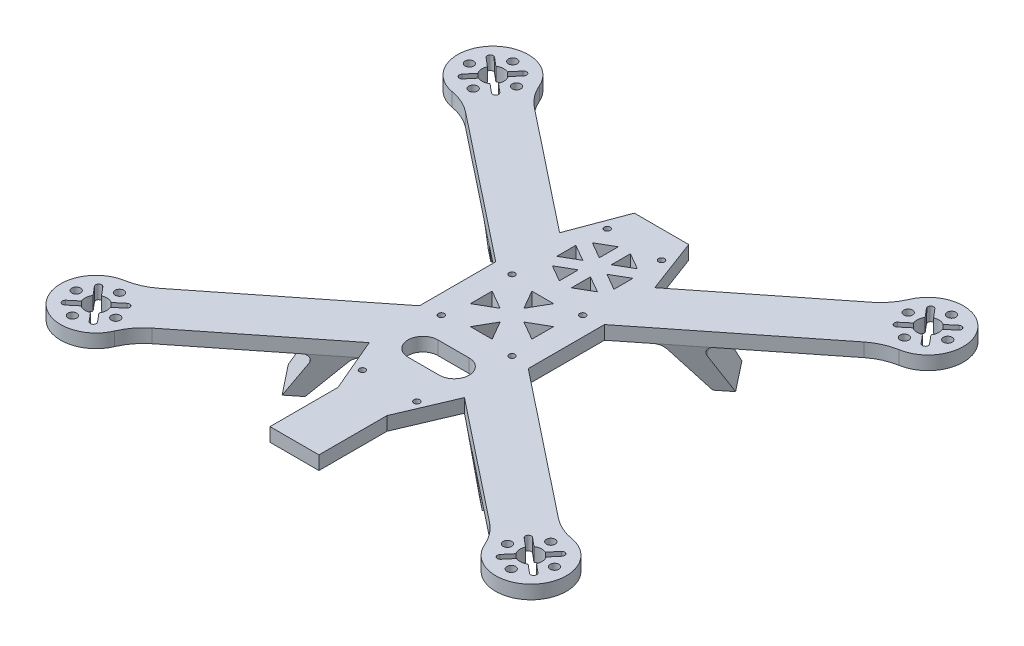
SolidWorks part; units mm, degrees
ref_plane "Front Plane" through (0, 0, 0) normal (0, 0, 1) x (1, 0, 0)
ref_plane "Top Plane" through (0, 0, 0) normal (0, 1, 0) x (1, 0, 0)
ref_plane "Right Plane" through (0, 0, 0) normal (1, 0, 0) x (0, 0, -1)
ref_axis "X Axis" through (-102.512, 0, 0) along (1, 0, 0)
ref_axis "Y Axis" through (0, 0, -107.1526) along (0, 0, 1)
ref_axis "Z Axis" through (0, 27.7441, 0) along (0, -1, 0)
ref_plane "Prop Guards Plane" through (0, 15, 0) normal (0, 1, 0) x (1, 0, 0)
ref_plane "Motor mount plane" through (0, 0, 0) normal (0, 1, 0) x (1, 0, 0)
sketch "Sketch1" plane through (0, 0, 0) normal (0, 1, 0) x (1, 0, 0)
  line L2 (-80, 73) -> (-80, 0) construction
  line L21 (-64.77, 0) -> (64.77, 0) construction
  line L22 (0, 59.69) -> (0, 20.32) construction
  line L25 (-93, 73) -> (-67, 73) construction
  line L27 (-80, 86) -> (-80, 60) construction
  line L36 (-88.3562, 63.0414) -> (-71.6438, 82.9586) construction
  line L38 (-89.9586, 81.3562) -> (-70.0414, 64.6438) construction
  line L40 (-85.1423, 66.8716) -> (-74.8577, 79.1284) construction
  line L41 (-85.9849, 67.5787) -> (-83.3147, 70.761)
  line L42 (-84.2997, 66.1646) -> (-81.6294, 69.3469)
  line L43 (-86.1284, 78.1423) -> (-73.8716, 67.8577) construction
  line L44 (-85.4213, 78.9849) -> (-82.239, 76.3147)
  line L45 (-86.8354, 77.2997) -> (-83.6531, 74.6294)
  line L49 (-78.3706, 76.6531) -> (-75.7003, 79.8354)
  line L50 (-77.761, 69.6853) -> (-74.5787, 67.0151)
  line L51 (-76.3469, 71.3706) -> (-73.1646, 68.7003)
  line L52 (-76.6853, 75.239) -> (-74.0151, 78.4213)
  line L53 (-80, 73) -> (0, 73) construction
  line L54 (-83.3147, 70.761) -> (-81.6294, 69.3469) construction
  line L56 (-77.761, 69.6853) -> (-76.3469, 71.3706) construction
  line L59 (-78.3706, 76.6531) -> (-76.6853, 75.239) construction
  line L61 (-82.239, 76.3147) -> (-83.6531, 74.6294) construction
  line L62 (0, -49.9102) -> (0, 49.9102) construction
  line L63 (78.3706, 76.6531) -> (75.7003, 79.8354)
  line L64 (76.6853, 75.239) -> (74.0151, 78.4213)
  line L65 (76.3469, 71.3706) -> (73.1646, 68.7003)
  line L66 (77.761, 69.6853) -> (74.5787, 67.0151)
  line L67 (84.2997, 66.1646) -> (81.6294, 69.3469)
  line L68 (85.9849, 67.5787) -> (83.3147, 70.761)
  line L69 (86.8354, 77.2997) -> (83.6531, 74.6294)
  line L70 (85.4213, 78.9849) -> (82.239, 76.3147)
  line L73 (-47.4403, 0) -> (47.4403, 0) construction
  line L85 (85.4213, -78.9849) -> (82.239, -76.3147)
  line L86 (86.8354, -77.2997) -> (83.6531, -74.6294)
  line L87 (85.9849, -67.5787) -> (83.3147, -70.761)
  line L88 (84.2997, -66.1646) -> (81.6294, -69.3469)
  line L89 (77.761, -69.6853) -> (74.5787, -67.0151)
  line L90 (76.3469, -71.3706) -> (73.1646, -68.7003)
  line L91 (76.6853, -75.239) -> (74.0151, -78.4213)
  line L92 (78.3706, -76.6531) -> (75.7003, -79.8354)
  line L93 (-76.6853, -75.239) -> (-74.0151, -78.4213)
  line L94 (-76.3469, -71.3706) -> (-73.1646, -68.7003)
  line L95 (-77.761, -69.6853) -> (-74.5787, -67.0151)
  line L96 (-78.3706, -76.6531) -> (-75.7003, -79.8354)
  line L97 (-86.8354, -77.2997) -> (-83.6531, -74.6294)
  line L98 (-85.4213, -78.9849) -> (-82.239, -76.3147)
  line L99 (-84.2997, -66.1646) -> (-81.6294, -69.3469)
  line L100 (-85.9849, -67.5787) -> (-83.3147, -70.761)
  line L101 (-87.9696, 72.3028) -> (-79.3028, 65.0304) construction
  line L102 (-79.3028, 65.0304) -> (-72.0304, 73.6972) construction
  line L103 (-72.0304, 73.6972) -> (-80.6972, 80.9696) construction
  line L104 (-80.6972, 80.9696) -> (-87.9696, 72.3028) construction
  circle A0 centre (-80, 73) radius 13
  circle A7 centre (-80, 73) radius 8 construction
  circle A9 centre (-87.9696, 72.3028) radius 1.6
  circle A10 centre (-79.3028, 65.0304) radius 1.6
  circle A11 centre (-80.6972, 80.9696) radius 1.6
  circle A12 centre (-72.0304, 73.6972) radius 1.6
  arc A13 (-83.6531, 74.6294) -> (-83.3147, 70.761) centre (-80, 73) ccw
  arc A14 (-85.9849, 67.5787) -> (-84.2997, 66.1646) centre (-85.1423, 66.8716) ccw
  arc A15 (-74.0151, 78.4213) -> (-75.7003, 79.8354) centre (-74.8577, 79.1284) ccw
  arc A16 (-85.4213, 78.9849) -> (-86.8354, 77.2997) centre (-86.1284, 78.1423) ccw
  arc A17 (-74.5787, 67.0151) -> (-73.1646, 68.7003) centre (-73.8716, 67.8577) ccw
  arc A18 (-81.6294, 69.3469) -> (-77.761, 69.6853) centre (-80, 73) ccw
  arc A19 (-76.3469, 71.3706) -> (-76.6853, 75.239) centre (-80, 73) ccw
  arc A20 (-78.3706, 76.6531) -> (-82.239, 76.3147) centre (-80, 73) ccw
  circle A21 centre (72.0304, 73.6972) radius 1.6
  circle A22 centre (79.3028, 65.0304) radius 1.6
  circle A23 centre (87.9696, 72.3028) radius 1.6
  circle A24 centre (80.6972, 80.9696) radius 1.6
  arc A25 (74.0151, 78.4213) -> (75.7003, 79.8354) centre (74.8577, 79.1284) cw
  arc A26 (76.3469, 71.3706) -> (76.6853, 75.239) centre (80, 73) cw
  arc A27 (74.5787, 67.0151) -> (73.1646, 68.7003) centre (73.8716, 67.8577) cw
  arc A28 (81.6294, 69.3469) -> (77.761, 69.6853) centre (80, 73) cw
  arc A29 (85.9849, 67.5787) -> (84.2997, 66.1646) centre (85.1423, 66.8716) cw
  arc A30 (83.6531, 74.6294) -> (83.3147, 70.761) centre (80, 73) cw
  arc A31 (85.4213, 78.9849) -> (86.8354, 77.2997) centre (86.1284, 78.1423) cw
  arc A32 (78.3706, 76.6531) -> (82.239, 76.3147) centre (80, 73) cw
  circle A33 centre (80, 73) radius 13
  circle A35 centre (80, -73) radius 13
  arc A36 (78.3706, -76.6531) -> (82.239, -76.3147) centre (80, -73) ccw
  arc A37 (85.4213, -78.9849) -> (86.8354, -77.2997) centre (86.1284, -78.1423) ccw
  arc A38 (83.6531, -74.6294) -> (83.3147, -70.761) centre (80, -73) ccw
  arc A39 (85.9849, -67.5787) -> (84.2997, -66.1646) centre (85.1423, -66.8716) ccw
  arc A40 (81.6294, -69.3469) -> (77.761, -69.6853) centre (80, -73) ccw
  arc A41 (74.5787, -67.0151) -> (73.1646, -68.7003) centre (73.8716, -67.8577) ccw
  arc A42 (76.3469, -71.3706) -> (76.6853, -75.239) centre (80, -73) ccw
  arc A43 (74.0151, -78.4213) -> (75.7003, -79.8354) centre (74.8577, -79.1284) ccw
  circle A44 centre (80.6972, -80.9696) radius 1.6
  circle A45 centre (87.9696, -72.3028) radius 1.6
  circle A46 centre (79.3028, -65.0304) radius 1.6
  circle A47 centre (72.0304, -73.6972) radius 1.6
  arc A48 (-78.3706, -76.6531) -> (-82.239, -76.3147) centre (-80, -73) cw
  arc A49 (-76.3469, -71.3706) -> (-76.6853, -75.239) centre (-80, -73) cw
  arc A50 (-81.6294, -69.3469) -> (-77.761, -69.6853) centre (-80, -73) cw
  arc A51 (-74.5787, -67.0151) -> (-73.1646, -68.7003) centre (-73.8716, -67.8577) cw
  arc A52 (-85.4213, -78.9849) -> (-86.8354, -77.2997) centre (-86.1284, -78.1423) cw
  arc A53 (-74.0151, -78.4213) -> (-75.7003, -79.8354) centre (-74.8577, -79.1284) cw
  arc A54 (-85.9849, -67.5787) -> (-84.2997, -66.1646) centre (-85.1423, -66.8716) cw
  arc A55 (-83.6531, -74.6294) -> (-83.3147, -70.761) centre (-80, -73) cw
  circle A56 centre (-72.0304, -73.6972) radius 1.6
  circle A57 centre (-80.6972, -80.9696) radius 1.6
  circle A58 centre (-79.3028, -65.0304) radius 1.6
  circle A59 centre (-87.9696, -72.3028) radius 1.6
  circle A60 centre (-80, -73) radius 13
  point P0 (0, 0)
  point P6 (0, 0)
  point P36 (-80, 73)
  point P53 (-80, 73)
  point P155 (-80, -73)
  point P156 (-80, -73)
  point P179 (0, 0)
  dimension "D3" = 26
  dimension "D4" = 16
  dimension "D7" = 1.1
  dimension "D5" = 3.2
  dimension "D6" = 40
  dimension "D9" = 16
  dimension "D8" = 8
  dimension "D10" = 2.2
  dimension "D2" = 80
  dimension "D11" = 73
extrude "Boss-Extrude3" add sketch "Sketch1" along normal blind 5
sketch "Sketch29" plane through (0, 0, 0) normal (0, 1, 0) x (1, 0, 0)
  line L5 (-67.0587, 74.2337) -> (-17.5, 35)
  line L6 (-17.5, -35) -> (17.5, -35)
  line L9 (-42.2793, 54.6169) -> (-53.452, 40.504) construction
  line L10 (-79.8381, 72.8718) -> (-47.8656, 47.5604) construction
  line L11 (-20, -14.0214) -> (-20, 14.0214)
  line L15 (-17.5, 35) -> (17.5, 35)
  line L22 (20, -14.0214) -> (20, 14.0214)
  line L23 (-17.5, -35) -> (17.5, 35) construction
  line L24 (-13, -13) -> (13, -13) construction
  line L25 (-13, -13) -> (-13, 13) construction
  line L26 (-13, 13) -> (13, 13) construction
  line L27 (13, -13) -> (13, 13) construction
  line L28 (-13, -13) -> (13, 13) construction
  line L29 (-13, 13) -> (13, -13) construction
  line L30 (-17.5, 35) -> (17.5, -35) construction
  line L31 (-78.2313, 60.1209) -> (-20, 14.0214)
  line L32 (42.2793, 54.6169) -> (53.452, 40.504) construction
  line L33 (49.1156, -37.0711) -> (37.943, -51.184) construction
  line L35 (-47.4403, 0) -> (47.4403, 0) construction
  line L36 (-67.0587, -74.2337) -> (-17.5, -35)
  line L37 (-78.2313, -60.1209) -> (-20, -14.0214)
  line L38 (0, -49.9102) -> (0, 49.9102) construction
  line L39 (67.0587, 74.2337) -> (17.5, 35)
  line L40 (78.2313, 60.1209) -> (20, 14.0214)
  line L41 (67.0587, -74.2337) -> (17.5, -35)
  line L42 (78.2313, -60.1209) -> (20, -14.0214)
  line L46 (0, -27) -> (0, 0) construction
  line L47 (-49.1156, -37.0711) -> (-37.943, -51.184) construction
  circle A1 centre (-13, 13) radius 1.1
  circle A2 centre (13, 13) radius 1.1
  circle A3 centre (13, -13) radius 1.1
  circle A4 centre (-13, -13) radius 1.1
  circle A11 centre (-80, 73) radius 13 construction
  circle A13 centre (-80, -73) radius 13 construction
  arc A14 (78.2313, -60.1209) -> (67.0587, -74.2337) centre (80, -73) ccw
  arc A15 (-78.2313, -60.1209) -> (-67.0587, -74.2337) centre (-80, -73) cw
  circle A16 centre (80, -73) radius 13 construction
  circle A17 centre (80, 73) radius 13 construction
  arc A18 (67.0587, 74.2337) -> (78.2313, 60.1209) centre (80, 73) ccw
  arc A20 (-67.0587, 74.2337) -> (-78.2313, 60.1209) centre (-80, 73) cw
  point P0 (0, 0)
  point P1 (0, 0)
  point P5 (0, 0)
  point P21 (0, 0)
  point P62 (-47.8656, 47.5604)
  dimension "D5" = 2.2
  dimension "D6" = 27
  dimension "D3" = 18
  dimension "D9" = 40
  dimension "D1" = 35
  dimension "D2" = 70
  dimension "D4" = 26
extrude "Boss-Extrude19" add sketch "Sketch29" along normal up to surface (5 mm away) up to face at (-80.6972, 5, -79.3696)
sketch "Sketch32" plane through (0, 0, 0) normal (0, 1, 0) x (1, 0, 0)
  line L0 (0, 0) -> (0, 55) construction
  line L1 (0, 0) -> (0, -80) construction
  line L4 (-10, 55) -> (-17.5, 35)
  line L6 (10, 55) -> (17.5, 35)
  line L7 (-10, 55) -> (10, 55)
  line L8 (-17.5, 35) -> (17.5, 35)
  line L9 (-9, -80) -> (9, -80)
  line L10 (-9, -80) -> (-9, -55)
  line L11 (-9, -55) -> (-17.5, -35)
  line L12 (-17.5, -35) -> (17.5, -35)
  line L13 (17.5, -35) -> (9, -55)
  line L14 (9, -55) -> (9, -80)
  line L15 (-9, -55) -> (9, -55) construction
  point P15 (0, -80)
  dimension "D1" = 55
  dimension "D2" = 20
  dimension "D3" = 80
  dimension "D5" = 18
extrude "Boss-Extrude20" add sketch "Sketch32" along normal up to surface (5 mm away) up to face at (-80.6972, 5, -79.3696)
sketch "Sketch33" plane through (0, 5, 0) normal (0, 1, 0) x (1, 0, 0)
  line L0 (0, 0) -> (0, -27) construction
  line L1 (-5.75, -27) -> (5.75, -27) construction
  line L2 (-5.75, -21.5) -> (5.75, -21.5)
  line L3 (-5.75, -32.5) -> (5.75, -32.5)
  line L4 (0, 19.5324) -> (0, -19.5324) construction
  line L5 (-9, 0) -> (0, 0) construction
  line L6 (-4.3812, 0) -> (-11.3094, 4)
  line L7 (-11.3094, 4) -> (-11.3094, -4)
  line L8 (-11.3094, -4) -> (-4.3812, 0)
  line L9 (0, 4.3812) -> (4, 11.3094)
  line L13 (4, 11.3094) -> (-4, 11.3094)
  line L14 (-4, 11.3094) -> (0, 4.3812)
  line L15 (4.3812, 0) -> (11.3094, -4)
  line L16 (11.3094, -4) -> (11.3094, 4)
  line L17 (11.3094, 4) -> (4.3812, 0)
  line L18 (0, -4.3812) -> (-4, -11.3094)
  line L19 (-4, -11.3094) -> (4, -11.3094)
  line L20 (4, -11.3094) -> (0, -4.3812)
  line L21 (-10, -45) -> (10, -45) construction
  line L22 (-10, 45) -> (10, 45) construction
  line L23 (-4.445, 30.48) -> (4.445, 30.48) construction
  line L24 (-4.445, 30.48) -> (-10.5072, 33.98)
  line L25 (-10.5072, 33.98) -> (-10.5072, 26.98)
  line L26 (-10.5072, 26.98) -> (-4.445, 30.48)
  line L27 (-2.2225, 34.3295) -> (-2.2225, 41.3295)
  line L28 (-2.2225, 41.3295) -> (-8.2847, 37.8295)
  line L29 (-8.2847, 37.8295) -> (-2.2225, 34.3295)
  line L30 (2.2225, 34.3295) -> (8.2847, 37.8295)
  line L31 (8.2847, 37.8295) -> (2.2225, 41.3295)
  line L32 (2.2225, 41.3295) -> (2.2225, 34.3295)
  line L33 (4.445, 30.48) -> (10.5072, 26.98)
  line L34 (10.5072, 26.98) -> (10.5072, 33.98)
  line L35 (10.5072, 33.98) -> (4.445, 30.48)
  line L36 (2.2225, 26.6305) -> (2.2225, 19.6305)
  line L37 (2.2225, 19.6305) -> (8.2847, 23.1305)
  line L38 (8.2847, 23.1305) -> (2.2225, 26.6305)
  line L39 (-2.2225, 26.6305) -> (-8.2847, 23.1305)
  line L40 (-8.2847, 23.1305) -> (-2.2225, 19.6305)
  line L41 (-2.2225, 19.6305) -> (-2.2225, 26.6305)
  arc A0 (-5.75, -21.5) -> (-5.75, -32.5) centre (-5.75, -27) ccw
  arc A1 (5.75, -32.5) -> (5.75, -21.5) centre (5.75, -27) ccw
  circle A2 centre (-9, 0) radius 2.3094 construction
  circle A3 centre (-10, -45) radius 1.1
  circle A4 centre (10, -45) radius 1.1
  circle A5 centre (-10, 45) radius 1.1
  circle A6 centre (10, 45) radius 1.1
  point P5 (0, -27)
  point P19 (0, -45)
  point P29 (0, 0)
  point P34 (0, 45)
  point P39 (-5.715, 30.48)
  point P40 (-4.445, 30.48)
  point P45 (0, 30.48)
  point P54 (0, 30.48)
  dimension "D3" = 11.5
  dimension "D8" = 2.2
  dimension "D11" = 7
  dimension "D1" = 27
  dimension "D2" = 11
  dimension "D4" = 8
  dimension "D5" = 9
  dimension "D7" = 45
  dimension "D9" = 20
  dimension "D10" = 45
  dimension "D6" = 4
  dimension "D12" = 6
extrude "Cut-Extrude1" cut sketch "Sketch33" against normal up to surface (5 mm away) contours L3 A1 L2 A0 | L6 L7 L8 | L15 L16 L17 | L9 L13 L14 | L18 L19 L20 | A5 | A6 | A3 | A4 | L27 L28 L29 | L24 L25 L26 | L33 L34 L35 | L30 L31 L32 | L39 L40 L41 | L36 L37 L38 up to face at (-72.0304, 0, -72.0972)
ref_plane "Stands Plane" through (0, -15, 0) normal (0, 1, 0) x (1, 0, 0)
sketch "Sketch30" plane through (0, -15, 0) normal (0, 1, 0) x (1, 0, 0)
  line L4 (-38.7981, -40.382) -> (0, 0) construction
  line L5 (-44.3728, -33.3164) -> (-33.2234, -47.4476) construction
  line L7 (-45.4952, -36.7558) -> (-36.8053, -47.7324)
  line L8 (-45.4952, -36.7558) -> (-40.7909, -33.0316)
  line L9 (-40.7909, -33.0316) -> (-32.1011, -44.0082)
  line L10 (-36.8053, -47.7324) -> (-32.1011, -44.0082)
  line L11 (-45.4952, -36.7558) -> (-32.1011, -44.0082) construction
  line L12 (-40.7909, -33.0316) -> (-36.8053, -47.7324) construction
  line L13 (-20, -14.0214) -> (-78.2313, -60.1209) construction
  line L14 (-67.0587, -74.2337) -> (-17.5, -35) construction
  point P0 (0, 0)
  point P1 (-38.7981, -40.382)
  point P13 (-38.7981, -40.382)
  dimension "D1" = 14
  dimension "D2" = 6
  dimension "D3" = 56
sketch "Sketch31" plane through (0, 0, 0) normal (0, -1, 0) x (1, 0, 0)
  line L1 (-31.7396, 23.3152) -> (-39.5801, 29.5222)
  line L2 (-31.7396, 23.3152) -> (-20.567, 37.428)
  line L3 (-20.567, 37.428) -> (-28.4075, 43.635)
  line L4 (-39.5801, 29.5222) -> (-28.4075, 43.635)
  line L5 (-31.7396, 23.3152) -> (-28.4075, 43.635) construction
  line L6 (-20.567, 37.428) -> (-39.5801, 29.5222) construction
  line L7 (-67.0587, 74.2337) -> (-17.5, 35) construction
  line L8 (-24.4885, 40.5325) -> (-35.6586, 26.4177) construction
  line L9 (-20, 14.0214) -> (-78.2313, 60.1209) construction
  line L10 (-30.0735, 33.4751) -> (0, 0) construction
  point P0 (-30.0735, 33.4751)
  point P7 (-30.0735, 33.4751)
  dimension "D1" = 45
  dimension "D2" = 10
loft "Loft1" add profiles "Sketch30", "Sketch31" connector at (-45.4952, -15, 36.7558) connector at (-39.5801, 0, 29.5222)
mirror "Mirror1" about plane through (0, 0, 0) normal (1, 0, 0) of bodies 235
mirror "Mirror2" about plane through (0, 0, 0) normal (0, 0, 1) of bodies 235 236
combine bodies "Combine2" operation type add bodies to combine 242 235 236 237 238
fillet "Fillet1" radius 2 4 edges
fillet "Fillet2" radius 5 4 edges
fillet "Fillet9" radius 20 8 edges at (-78.2313, 2.5, -60.1209) (-78.2313, 2.5, 60.1209) (-67.0587, 2.5, 74.2337) (67.0587, 2.5, 74.2337) (78.2313, 2.5, 60.1209) (67.0587, 2.5, -74.2337) (78.2313, 2.5, -60.1209) (-67.0587, 2.5, -74.2337)
fillet "Fillet10" [suppressed] radius 2
fillet "Fillet11" [suppressed] radius 2
equation "\"Prop Dia\"= 76.2mm"
equation "\"ground_clearance\"= 15mm"
equation "\"D1@Prop Guards Plane\"=\"ground_clearance\""
